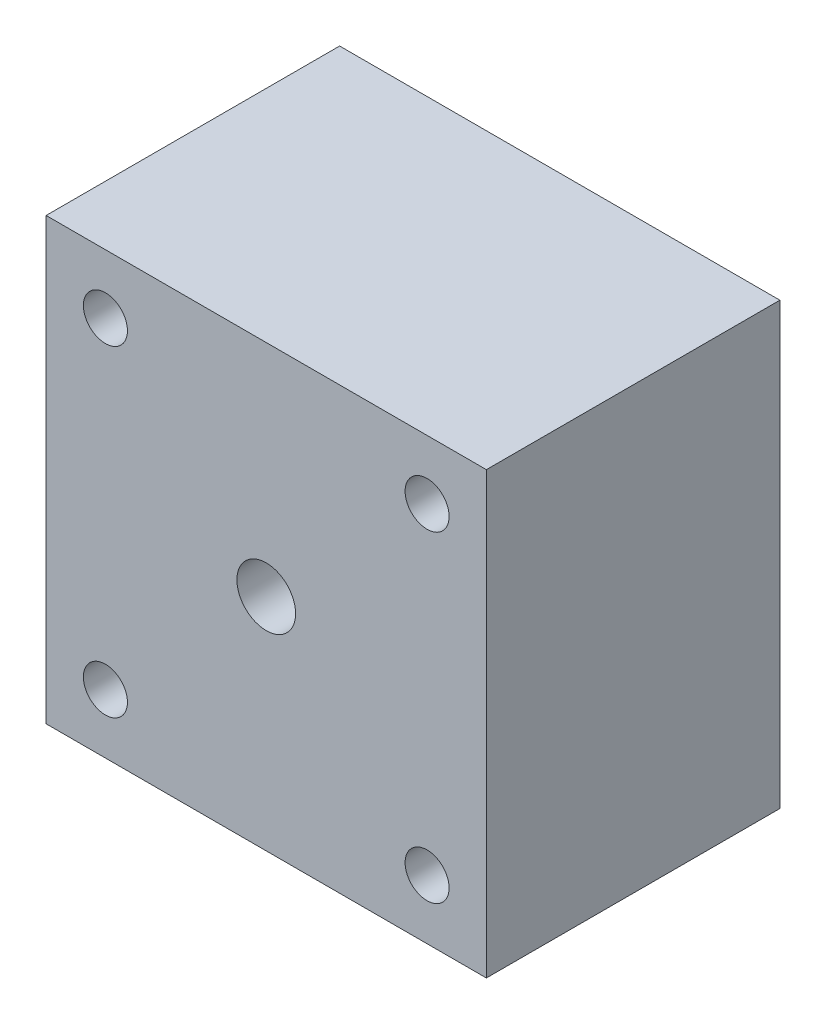
SolidWorks part; units mm, degrees
other "Markup1"
sketch "Sketch2" plane through (-15, -15, 20) normal (-0.8626, -0.0457, 0.5038) x (0.0966, -0.9925, 0.0754)
ref_plane "Front Plane" through (0, 0, 0) normal (0, 0, 1) x (1, 0, 0)
ref_plane "Top Plane" through (0, 0, 0) normal (0, 1, 0) x (1, 0, 0)
ref_plane "Right Plane" through (0, 0, 0) normal (1, 0, 0) x (0, 0, -1)
sketch "Sketch1" plane through (0, 0, 0) normal (0, 0, 1) x (1, 0, 0)
  line L0 (0, 10.9602) -> (0, -10.9602)
  line L1 (15, -15) -> (-15, -15)
  line L2 (15, -15) -> (15, 15)
  line L3 (15, 15) -> (-15, 15)
  line L4 (-15, -15) -> (-15, 15)
  line L5 (15, -15) -> (-15, 15) construction
  line L6 (15, 15) -> (-15, -15) construction
  line L7 (10.9602, -10.9602) -> (-10.9602, -10.9602)
  line L8 (10.9602, -10.9602) -> (10.9602, 10.9602)
  line L9 (10.9602, 10.9602) -> (-10.9602, 10.9602)
  line L10 (-10.9602, -10.9602) -> (-10.9602, 10.9602)
  line L11 (10.9602, -10.9602) -> (-10.9602, 10.9602) construction
  line L12 (10.9602, 10.9602) -> (-10.9602, -10.9602) construction
  line L13 (-10.9602, 0) -> (10.9602, 0)
  circle A0 centre (-10.9602, 10.9602) radius 1.5
  circle A1 centre (10.9602, 10.9602) radius 1.5
  circle A2 centre (10.9602, -10.9602) radius 1.5
  circle A3 centre (-10.9602, -10.9602) radius 1.5
  point P0 (0, 0)
  point P6 (0, 0)
  dimension "D2" = 3
  dimension "D1" = 31
  dimension "D3" = 30
extrude "Boss-Extrude1" add sketch "Sketch1" along normal blind 20 contours L4 L1 L2 L3 L7 A3 L10 A0 L9 A1 L8 A2 | A0 L10 L13 L0 L9 | L8 A1 L9 L0 L13 | L10 A3 L7 L0 L13 | A2 L8 L13 L0 L7 region at (5.4078, 5.4078, 0) region at (-5.4078, 5.4078, 0) region at (5.4078, -5.4078, 0) region at (-5.4078, -5.4078, 0) region at (0, -14.5757, 0)
sketch "Sketch3" plane through (0, 0, 20) normal (0, 0, 1) x (1, 0, 0)
  circle A0 centre (0, 0) radius 2
  dimension "D1" = 4
extrude "Cut-Extrude1" cut sketch "Sketch3" against normal blind 10
equation "\"a\"=30"
equation "\"D3@Sketch1\"=\"a\""
equation "\"b\"=20"
equation "\"D1@Boss-Extrude1\"=\"b\""
